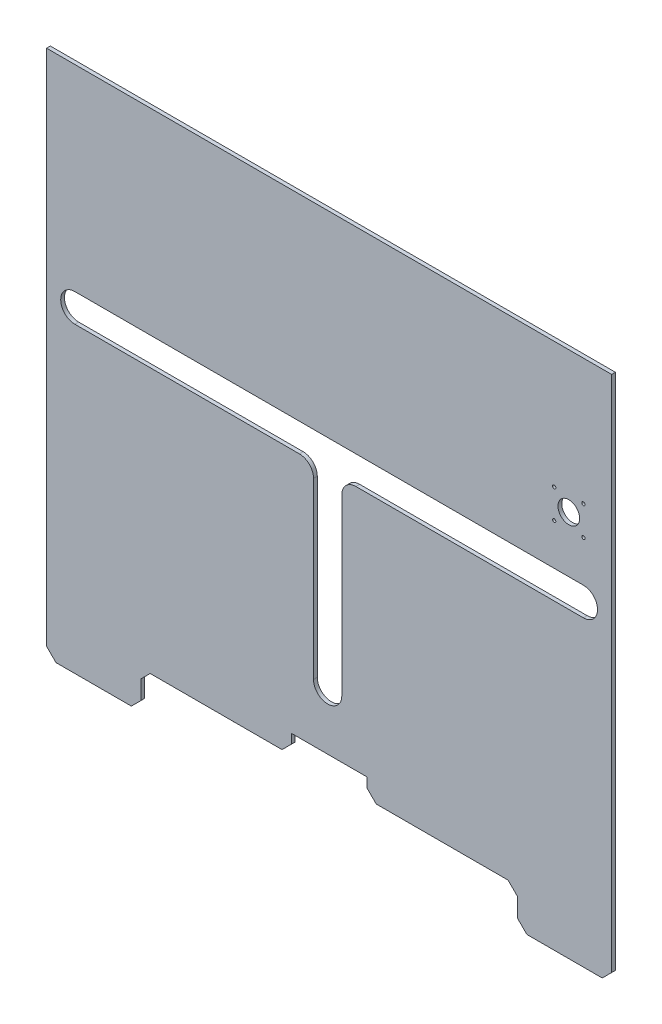
SolidWorks part; units mm, degrees
ref_plane "Front Plane" through (0, 0, 0) normal (0, 0, 1) x (1, 0, 0)
ref_plane "Top Plane" through (0, 0, 0) normal (0, 1, 0) x (1, 0, 0)
ref_plane "Right Plane" through (0, 0, 0) normal (1, 0, 0) x (0, 0, -1)
sketch "Sketch1" plane through (0, 0, 0) normal (0, 0, 1) x (1, 0, 0)
  line L0 (460.3197, -451.5188) -> (460.3197, -431.5188)
  line L1 (450.3197, -421.5188) -> (310.3197, -421.5188)
  line L2 (560.3197, -5.0048) -> (560.3197, 98.4812)
  line L3 (60.3197, -431.5188) -> (60.3197, -451.5188)
  line L4 (560.3197, 98.4812) -> (540.3197, 98.4812)
  line L5 (540.3197, 88.4812) -> (540.3197, -420.0048) construction
  line L6 (560.3197, -5.0048) -> (560.3197, -420.0048)
  line L7 (0.3197, 98.4812) -> (540.3197, 98.4812)
  line L8 (2.3197, -461.5188) -> (50.3197, -461.5188)
  line L9 (470.3197, -461.5188) -> (540.3197, -461.5188)
  line L10 (460.3197, -431.5188) -> (450.3197, -421.5188)
  line L11 (530.3197, -23.973) -> (530.3197, -80.4204) construction
  line L12 (-39.6803, -421.5188) -> (-39.6803, -5.0048)
  line L13 (530.3197, -35.4482) -> (499.3197, -35.4482) construction
  line L14 (470.3197, -461.5188) -> (460.3197, -451.5188)
  line L15 (499.3197, -35.4482) -> (499.3197, -66.4482) construction
  line L16 (499.3197, -66.4482) -> (530.3197, -66.4482) construction
  line L17 (530.3197, -66.4482) -> (499.3197, -35.4482) construction
  line L18 (0.3197, 98.4812) -> (-39.6803, 98.4812)
  line L19 (-39.6803, 98.4812) -> (-39.6803, -5.0048)
  line L20 (-39.6803, -421.5188) -> (-39.6803, -451.5188)
  line L21 (-29.6803, -461.5188) -> (2.3197, -461.5188)
  line L22 (560.3197, -420.0048) -> (560.3197, -451.5188)
  line L23 (550.3197, -461.5188) -> (540.3197, -461.5188)
  line L24 (70.3197, -421.5188) -> (60.3197, -431.5188)
  line L25 (60.3197, -451.5188) -> (50.3197, -461.5188)
  line L26 (560.3197, -451.5188) -> (550.3197, -461.5188)
  line L27 (-39.6803, -451.5188) -> (-29.6803, -461.5188)
  line L28 (300.3197, -411.5188) -> (300.3197, -401.5188)
  line L29 (300.3197, -401.5188) -> (220.3197, -401.5188)
  line L30 (220.3197, -401.5188) -> (220.3197, -411.5188)
  line L31 (210.3197, -421.5188) -> (70.3197, -421.5188)
  line L32 (310.3197, -421.5188) -> (300.3197, -411.5188)
  line L33 (220.3197, -411.5188) -> (210.3197, -421.5188)
  circle A0 centre (499.3197, -35.4482) radius 1.75
  circle A1 centre (499.3197, -66.4482) radius 1.75
  circle A2 centre (530.3197, -66.4482) radius 1.75
  circle A3 centre (530.3197, -35.4482) radius 1.75
  circle A4 centre (514.8197, -50.9482) radius 11.5
  point P0 (460.3197, -461.5188)
  point P5 (460.3197, -421.5188)
  point P27 (-39.6803, -461.5188)
  point P28 (560.3197, -461.5188)
  point P29 (60.3197, -421.5188)
  point P30 (60.3197, -461.5188)
  point P42 (300.3197, -421.5188)
  point P46 (220.3197, -421.5188)
  dimension "D6" = 23
  dimension "D7" = 3.5
  dimension "D1" = 560
  dimension "D2" = 10
  dimension "D3" = 600
  dimension "D4" = 100
  dimension "D5" = 31
  dimension "D8" = 10
  dimension "D9" = 100
  dimension "D11" = 80
  dimension "D18" = 20
  dimension "D19" = 40
extrude "Boss-Extrude1" add sketch "Sketch1" along normal blind 4
sketch "Sketch2" plane through (0, 0, 4) normal (0, 0, 1) x (1, 0, 0)
  line L0 (-9.6803, -110.3334) -> (530.3197, -110.3334)
  line L1 (530.3197, -140.3334) -> (-9.6803, -140.3334)
  line L2 (-29.6803, -461.5188) -> (50.3197, -461.5188) construction
  line L4 (560.3197, 98.4812) -> (-39.6803, 98.4812) construction
  arc A0 (-9.6803, -110.3334) -> (-9.6803, -140.3334) centre (-9.6803, -125.3334) ccw
  arc A1 (530.3197, -140.3334) -> (530.3197, -110.3334) centre (530.3197, -125.3334) ccw
  point P8 (260.3197, -140.3334)
  point P11 (260.3197, 98.4812)
  dimension "D2" = 15
  dimension "D1" = 540
  dimension "D3" = 0
extrude "Cut-Extrude1" cut sketch "Sketch2" against normal blind 10
sketch "Sketch3" plane through (0, 0, 0) normal (0, 0, -1) x (-1, 0, 0)
  line L0 (-273.7635, -140.3334) -> (-273.7635, -340.3334)
  line L1 (9.6803, -140.3334) -> (-530.3197, -140.3334) construction
  line L2 (-243.7635, -340.3334) -> (-243.7635, -140.3334)
  line L3 (-243.7635, -140.3334) -> (-273.7635, -140.3334)
  arc A0 (-273.7635, -340.3334) -> (-243.7635, -340.3334) centre (-258.7635, -340.3334) ccw
  dimension "D2" = 15
  dimension "D1" = 200
extrude "Cut-Extrude2" cut sketch "Sketch3" against normal blind 10
fillet "Fillet1" radius 15 2 edges at (243.7635, -140.3334, 2) (273.7635, -140.3334, 2)
